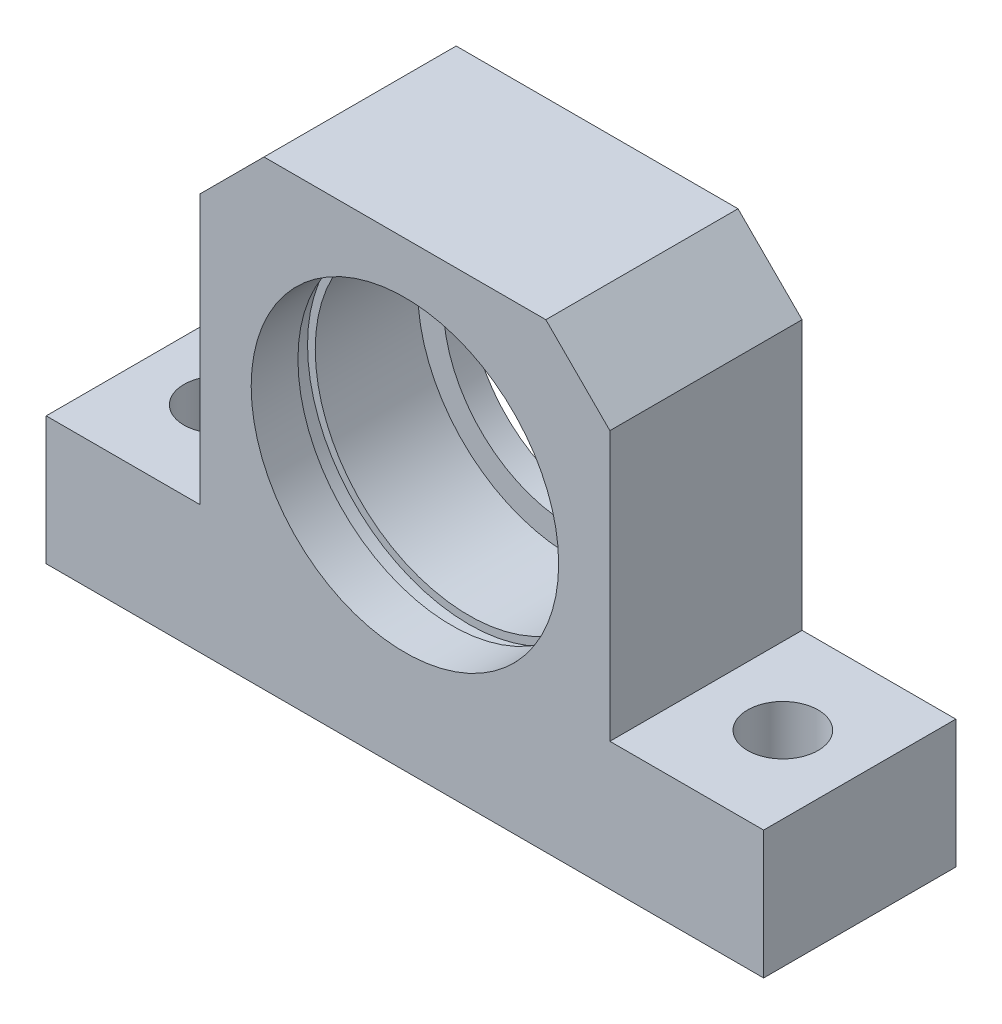
SolidWorks part; units mm, degrees
ref_plane "Front Plane" through (0, 0, 0) normal (0, 0, 1) x (1, 0, 0)
ref_plane "Top Plane" through (0, 0, 0) normal (0, 1, 0) x (1, 0, 0)
ref_plane "Right Plane" through (0, 0, 0) normal (1, 0, 0) x (0, 0, -1)
sketch "Sketch1" plane through (0, 0, 0) normal (0, 0, 1) x (1, 0, 0)
  line L0 (-16, 36) -> (16, 36)
  line L1 (16, 36) -> (16, 10)
  line L2 (16, 10) -> (28, 10)
  line L3 (28, 10) -> (28, 0)
  line L4 (28, 0) -> (-28, 0)
  line L5 (-28, 0) -> (-28, 10)
  line L6 (-28, 10) -> (-16, 10)
  line L7 (-16, 10) -> (-16, 36)
  line L8 (0, 36) -> (0, 0) construction
  point P12 (0, 20)
  dimension "L" = 56
  dimension "S" = 10
  dimension "L2" = 32
  dimension "H_s" = 20
  dimension "H" = 36
  dimension "MSM_6" = 16
extrude "Boss-Extrude1" add sketch "Sketch1" against normal blind 15
sketch "Sketch2" plane through (0, 0, 0) normal (1, 0, 0) x (0, 0, -1)
  line L0 (15, 20) -> (0, 20) construction
  line L1 (3.65, 32) -> (3.65, 32.6)
  line L2 (13, 32) -> (5, 32)
  line L3 (13, 32) -> (13, 30)
  line L4 (13, 30) -> (15, 30)
  line L5 (3.65, 32.6) -> (5, 32.6)
  line L6 (5, 32.6) -> (5, 32)
  line L7 (0, 32) -> (0, 20)
  line L8 (0, 20) -> (15, 20)
  line L9 (15, 20) -> (15, 30)
  line L11 (0, 10) -> (0, 36) construction
  line L12 (3.65, 32) -> (0, 32)
  line L13 (0, 10) -> (0, 36) construction
  line L14 (15, 10) -> (15, 36) construction
  dimension "D" = 24
  dimension "DH_s" = 20
  dimension "B" = 8
  dimension "H_s" = 20
  dimension "L1_s" = 2
  dimension "MSM_2" = 1.35
  dimension "MSM_1" = 25.2
revolve "Cut-Revolve1" cut sketch "Sketch2" angle 360 about L0
hole_wizard "Diameter Hole1" positions "Sketch4" profile "Sketch3" hole size "Ø5.5" standard "JIS" end condition through all
sketch "Sketch4" plane through (0, 10, 0) normal (0, 1, 0) x (1, 0, 0)
  line L10 (0, 0) -> (0, 15) construction
  line L11 (16, 15) -> (-16, 15) construction
  line L12 (-28, 7.5) -> (28, 7.5) construction
  line L13 (-28, 15) -> (-28, 0) construction
  line L14 (28, 15) -> (28, 0) construction
  point P0 (-22, 7.5)
  point P6 (22, 7.5)
  dimension "L1" = 44
  dimension "T/2" = 7.5
sketch "Sketch3" plane through (-22, 10, -7.5) normal (1, 0, 0) x (0, 0, 1)
  line L0 (0, 0) -> (0, 10)
  line L1 (0, 10) -> (2.75, 10)
  line L2 (2.75, 10) -> (2.75, 0)
  line L5 (2.75, 0) -> (0, 0)
  line L11 (0, 0) -> (0, 10) construction
  dimension "D1_s" = 5.5
  dimension "Thru Hole Depth" = 10
chamfer "Chamfer1" distance 5 angle 45 2 edges at (-16, 36, -7.5) (16, 36, -7.5)
chamfer "Chamfer2" [suppressed] distance 2 angle 45
